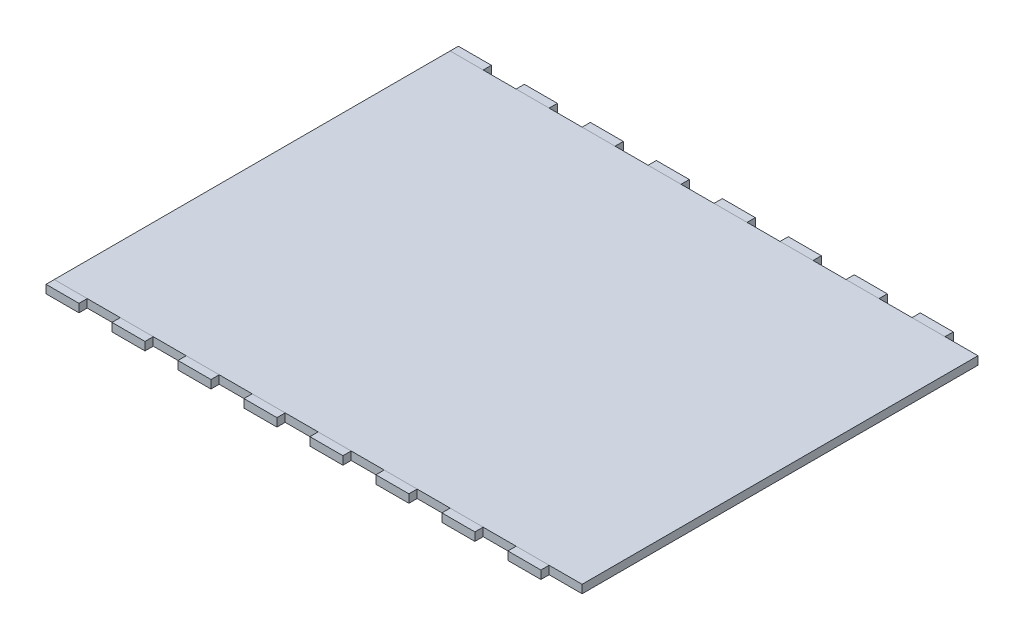
SolidWorks part; units mm, degrees
ref_plane "Front" through (0, 0, 0) normal (0, 0, 1) x (1, 0, 0)
ref_plane "Top" through (0, 0, 0) normal (0, 1, 0) x (1, 0, 0)
ref_plane "Right" through (0, 0, 0) normal (1, 0, 0) x (0, 0, -1)
sketch "Sketch1" plane through (0, 0, 0) normal (0, 1, 0) x (1, 0, 0)
  line L1 (0, 0) -> (203.2, 0)
  line L2 (0, 0) -> (0, 152.4)
  line L3 (0, 152.4) -> (203.2, 152.4)
  line L4 (203.2, 0) -> (203.2, 152.4)
  dimension "D1" = 203.2
  dimension "D2" = 152.4
extrude "Boss-Extrude1" add sketch "Sketch1" along normal blind 3.175
sketch "Sketch2" plane through (0, 3.175, 0) normal (0, 1, 0) x (1, 0, 0)
  line L0 (25.4, 0) -> (25.4, -3.175)
  line L1 (0, 0) -> (12.7, 0)
  line L2 (0, 0) -> (0, -3.175)
  line L3 (0, -3.175) -> (12.7, -3.175)
  line L4 (12.7, 0) -> (12.7, -3.175)
  line L5 (25.4, 0) -> (38.1, 0)
  line L6 (38.1, 0) -> (38.1, -3.175)
  line L7 (25.4, -3.175) -> (38.1, -3.175)
  line L8 (50.8, 0) -> (50.8, -3.175)
  line L9 (50.8, 0) -> (63.5, 0)
  line L10 (63.5, 0) -> (63.5, -3.175)
  line L11 (50.8, -3.175) -> (63.5, -3.175)
  line L12 (76.2, 0) -> (76.2, -3.175)
  line L13 (76.2, 0) -> (88.9, 0)
  line L14 (88.9, 0) -> (88.9, -3.175)
  line L15 (76.2, -3.175) -> (88.9, -3.175)
  line L16 (101.6, 0) -> (101.6, -3.175)
  line L17 (101.6, 0) -> (114.3, 0)
  line L18 (114.3, 0) -> (114.3, -3.175)
  line L19 (101.6, -3.175) -> (114.3, -3.175)
  line L20 (127, 0) -> (127, -3.175)
  line L21 (127, 0) -> (139.7, 0)
  line L22 (139.7, 0) -> (139.7, -3.175)
  line L23 (127, -3.175) -> (139.7, -3.175)
  line L24 (152.4, 0) -> (152.4, -3.175)
  line L25 (152.4, 0) -> (165.1, 0)
  line L26 (165.1, 0) -> (165.1, -3.175)
  line L27 (152.4, -3.175) -> (165.1, -3.175)
  line L28 (177.8, 0) -> (177.8, -3.175)
  line L29 (177.8, 0) -> (190.5, 0)
  line L30 (190.5, 0) -> (190.5, -3.175)
  line L31 (177.8, -3.175) -> (190.5, -3.175)
  line L32 (0, 76.2) -> (203.2, 76.2) construction
  line L33 (0, 152.4) -> (0, 0) construction
  line L34 (203.2, 0) -> (203.2, 152.4) construction
  line L35 (177.8, 152.4) -> (190.5, 152.4)
  line L36 (190.5, 152.4) -> (190.5, 155.575)
  line L37 (177.8, 155.575) -> (190.5, 155.575)
  line L38 (177.8, 152.4) -> (177.8, 155.575)
  line L39 (152.4, 152.4) -> (165.1, 152.4)
  line L40 (165.1, 152.4) -> (165.1, 155.575)
  line L41 (152.4, 155.575) -> (165.1, 155.575)
  line L42 (152.4, 152.4) -> (152.4, 155.575)
  line L43 (127, 152.4) -> (139.7, 152.4)
  line L44 (139.7, 152.4) -> (139.7, 155.575)
  line L45 (127, 155.575) -> (139.7, 155.575)
  line L46 (127, 152.4) -> (127, 155.575)
  line L47 (101.6, 152.4) -> (114.3, 152.4)
  line L48 (114.3, 152.4) -> (114.3, 155.575)
  line L49 (101.6, 155.575) -> (114.3, 155.575)
  line L50 (101.6, 152.4) -> (101.6, 155.575)
  line L51 (76.2, 152.4) -> (88.9, 152.4)
  line L52 (88.9, 152.4) -> (88.9, 155.575)
  line L53 (76.2, 155.575) -> (88.9, 155.575)
  line L54 (76.2, 152.4) -> (76.2, 155.575)
  line L55 (50.8, 152.4) -> (63.5, 152.4)
  line L56 (63.5, 152.4) -> (63.5, 155.575)
  line L57 (50.8, 155.575) -> (63.5, 155.575)
  line L58 (50.8, 152.4) -> (50.8, 155.575)
  line L59 (25.4, 152.4) -> (38.1, 152.4)
  line L60 (38.1, 152.4) -> (38.1, 155.575)
  line L61 (25.4, 155.575) -> (38.1, 155.575)
  line L62 (25.4, 152.4) -> (25.4, 155.575)
  line L63 (0, 155.575) -> (12.7, 155.575)
  line L64 (12.7, 152.4) -> (12.7, 155.575)
  line L65 (0, 152.4) -> (12.7, 152.4)
  line L66 (0, 152.4) -> (0, 155.575)
  dimension "D1" = 3.175
  dimension "D2" = 12.7
  dimension "D3" = 8
extrude "Boss-Extrude2" add sketch "Sketch2" against normal blind 3.175 separate body
